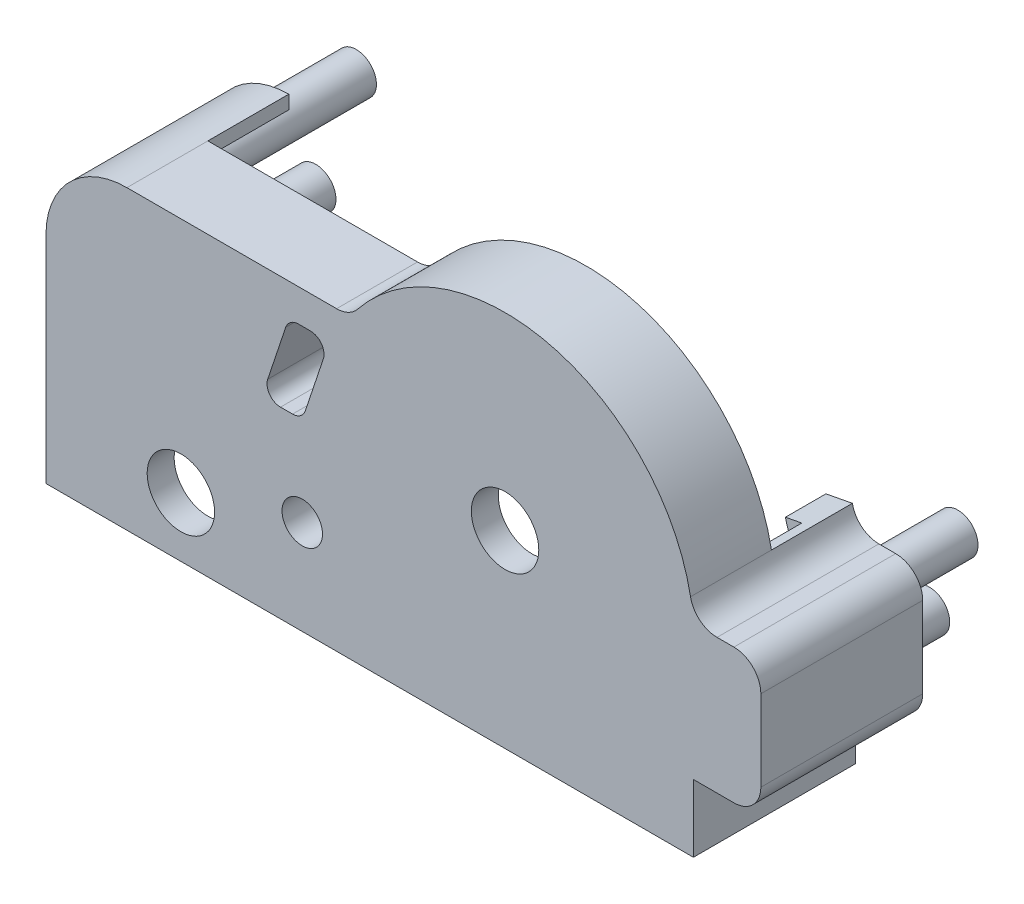
SolidWorks part; units mm, degrees
ref_plane "Front Plane" through (0, 0, 0) normal (0, 0, 1) x (1, 0, 0)
ref_plane "Top Plane" through (0, 0, 0) normal (0, 1, 0) x (1, 0, 0)
ref_plane "Right Plane" through (0, 0, 0) normal (1, 0, 0) x (0, 0, -1)
sketch "Sketch1" plane through (0, 0, 0) normal (0, 0, 1) x (1, 0, 0)
  line L0 (-17.0179, -7) -> (6.9821, -7)
  line L1 (-17.0179, -7) -> (-17.0179, 1)
  line L2 (-14.0179, 4) -> (-6.245, 4)
  line L3 (6.9821, -7) -> (6.9821, -4.5)
  line L4 (6.9821, -4.5) -> (8.4821, -4.5)
  line L5 (9.4821, -3.5) -> (9.4821, -0.5)
  line L6 (8.4821, 0.5) -> (7.8581, 0.5)
  arc A0 (-14.0179, 4) -> (-17.0179, 1) centre (-14.0179, 1) ccw
  arc A1 (6.8759, 1.3125) -> (-5.4644, 4.375) centre (0, 0) ccw
  arc A2 (9.4821, -0.5) -> (8.4821, 0.5) centre (8.4821, -0.5) ccw
  arc A3 (8.4821, -4.5) -> (9.4821, -3.5) centre (8.4821, -3.5) ccw
  arc A5 (-6.245, 4) -> (-5.4644, 4.375) centre (-6.245, 5) ccw
  arc A6 (6.8759, 1.3125) -> (7.8581, 0.5) centre (7.8581, 1.5) ccw
  point P8 (-17.0179, 4)
  point P15 (9.4821, 0.5)
  point P18 (9.4821, -4.5)
  point P21 (6.9821, -4.5)
  point P26 (6.9821, 0.5)
  dimension "D4" = 3
  dimension "D5" = 14
  dimension "D10" = 1
  dimension "D11" = 1
  dimension "D1" = 7
  dimension "D2" = 24
  dimension "D3" = 11
  dimension "D6" = 2.5
  dimension "D7" = 2.5
  dimension "D8" = 5
  dimension "D9" = 2.5
extrude "Boss-Extrude1" add sketch "Sketch1" along normal blind 6
shell "Shell1" thickness 1 removed face at (-5.0179, -7, 3) removed face at (0.4256, -0.539, 0)
sketch "Sketch2" plane through (0, 0, 5) normal (0, 0, -1) x (-1, 0, 0)
  line L0 (16.0179, -7) -> (-5.9821, -7) construction
  line L1 (17.0179, 1) -> (17.0179, -7) construction
  line L2 (7.2116, 2.8) -> (7.6575, 2.8)
  line L3 (6.7373, 2.1419) -> (7.4039, 0.1419)
  line L4 (8.1318, 2.4581) -> (8.7985, 0.4581)
  line L5 (7.8783, -0.2) -> (8.3242, -0.2)
  line L6 (6.245, 4) -> (14.0179, 4) construction
  circle A0 centre (0, 0) radius 1.25
  circle A1 centre (7.5179, -3.5) radius 0.75
  circle A2 centre (12.0179, -4.7966) radius 1.25
  arc A3 (6.7373, 2.1419) -> (7.2116, 2.8) centre (7.2116, 2.3) cw
  arc A4 (7.6575, 2.8) -> (8.1318, 2.4581) centre (7.6575, 2.3) cw
  arc A5 (8.7985, 0.4581) -> (8.3242, -0.2) centre (8.3242, 0.3) cw
  arc A6 (7.4039, 0.1419) -> (7.8783, -0.2) centre (7.8783, 0.3) ccw
  point P20 (6.5179, 2.8)
  point P23 (8.0179, 2.8)
  point P26 (9.0179, -0.2)
  dimension "D1" = 2.5
  dimension "D2" = 1.5
  dimension "D4" = 3.5
  dimension "D5" = 2.5
  dimension "D6" = 2.2034
  dimension "D7" = 5
  dimension "D13" = 0.5
  dimension "D3" = 9.5
  dimension "D8" = 9
  dimension "D9" = 8
  dimension "D10" = 3
  dimension "D11" = 1.5
  dimension "D12" = 1.2
extrude "Cut-Extrude1" cut sketch "Sketch2" against normal blind 6
sketch "Sketch3" plane through (0, -7, 0) normal (0, -1, 0) x (1, 0, 0)
  line L0 (-5.1962, 5) -> (-5.1962, 0) construction
  line L1 (5.9821, 5) -> (-5.1962, 5)
  line L2 (5.9821, 5) -> (5.9821, 2)
  line L3 (5.9821, 2) -> (-5.1962, 2)
  line L4 (-5.1962, 5) -> (-5.1962, 2)
  dimension "D1" = 3
extrude "Boss-Extrude2" add sketch "Sketch3" against normal blind 1
sketch "Sketch6" plane through (0, 0, 0) normal (0, 0, -1) x (-1, 0, 0)
  line L0 (6.245, 4) -> (14.0179, 4) construction
  line L1 (6.245, 3) -> (14.0179, 3) construction
  line L2 (6.245, 4) -> (14.0179, 4)
  line L3 (6.245, 3) -> (14.0179, 3)
  line L4 (-6.8759, 1.3125) -> (-5.8936, 1.125)
  line L5 (14.0179, 4) -> (14.0179, 3)
  arc A0 (5.4644, 4.375) -> (6.245, 4) centre (6.245, 5) ccw construction
  arc A1 (4.6837, 3.75) -> (6.245, 3) centre (6.245, 5) ccw construction
  arc A2 (4.6837, 3.75) -> (-5.8936, 1.125) centre (0, 0) ccw construction
  arc A3 (5.4644, 4.375) -> (-6.8759, 1.3125) centre (0, 0) ccw construction
  arc A4 (5.4644, 4.375) -> (6.245, 4) centre (6.245, 5) ccw
  arc A5 (4.6837, 3.75) -> (6.245, 3) centre (6.245, 5) ccw
  arc A6 (4.6837, 3.75) -> (-5.8936, 1.125) centre (0, 0) ccw
  arc A7 (5.4644, 4.375) -> (-6.8759, 1.3125) centre (0, 0) ccw
extrude "Cut-Extrude2" cut sketch "Sketch6" against normal blind 3
sketch "Sketch7" plane through (0, 0, 5) normal (0, 0, -1) x (-1, 0, 0)
  circle A0 centre (0, 0) radius 6
  circle A1 centre (0, 0) radius 7
  dimension "D1" = 12
  dimension "D2" = 14
extrude "Boss-Extrude4" add sketch "Sketch7" along normal blind 2
sketch "Sketch8" plane through (0, 0, 5) normal (0, 0, -1) x (-1, 0, 0)
  line L0 (7.6575, 2.8) -> (7.2116, 2.8) construction
  line L1 (8.7985, 0.4581) -> (8.1318, 2.4581) construction
  line L2 (7.8783, -0.2) -> (8.3242, -0.2) construction
  line L3 (6.7373, 2.1419) -> (7.4039, 0.1419) construction
  line L4 (7.6575, 2.8) -> (7.2116, 2.8)
  line L5 (8.7985, 0.4581) -> (8.1318, 2.4581)
  line L6 (7.8783, -0.2) -> (8.3242, -0.2)
  line L7 (6.7373, 2.1419) -> (7.4039, 0.1419)
  line L8 (5.9783, 1.8889) -> (6.645, -0.1111)
  line L9 (7.8783, -1) -> (8.3242, -1)
  line L10 (9.5575, 0.7111) -> (8.8908, 2.7111)
  line L11 (7.6575, 3.6) -> (7.2116, 3.6)
  circle A0 centre (7.5179, -3.5) radius 0.75 construction
  arc A1 (7.2116, 2.8) -> (6.7373, 2.1419) centre (7.2116, 2.3) ccw construction
  arc A2 (8.1318, 2.4581) -> (7.6575, 2.8) centre (7.6575, 2.3) ccw construction
  arc A3 (8.3242, -0.2) -> (8.7985, 0.4581) centre (8.3242, 0.3) ccw construction
  arc A4 (7.4039, 0.1419) -> (7.8783, -0.2) centre (7.8783, 0.3) ccw construction
  circle A5 centre (7.5179, -3.5) radius 0.75
  arc A6 (7.2116, 2.8) -> (6.7373, 2.1419) centre (7.2116, 2.3) ccw
  arc A7 (8.1318, 2.4581) -> (7.6575, 2.8) centre (7.6575, 2.3) ccw
  arc A8 (8.3242, -0.2) -> (8.7985, 0.4581) centre (8.3242, 0.3) ccw
  arc A9 (7.4039, 0.1419) -> (7.8783, -0.2) centre (7.8783, 0.3) ccw
  arc A10 (6.645, -0.1111) -> (7.8783, -1) centre (7.8783, 0.3) ccw
  arc A11 (8.3242, -1) -> (9.5575, 0.7111) centre (8.3242, 0.3) ccw
  arc A12 (8.8908, 2.7111) -> (7.6575, 3.6) centre (7.6575, 2.3) ccw
  arc A13 (7.2116, 3.6) -> (5.9783, 1.8889) centre (7.2116, 2.3) ccw
  circle A14 centre (7.5179, -3.5) radius 1.55
  dimension "D1" = 0.8
extrude "Boss-Extrude5" add sketch "Sketch8" along normal blind 2
sketch "Sketch10" plane through (0, 0, 5) normal (0, 0, -1) x (-1, 0, 0)
  line L0 (17.0179, 1) -> (17.0179, -7) construction
  line L1 (17.0179, -7) -> (16.0179, -7) construction
  line L2 (16.0179, 1) -> (16.0179, -7) construction
  line L3 (-9.4821, -3.5) -> (-9.4821, -0.5) construction
  line L5 (-8.4821, 0.5) -> (-7.8581, 0.5) construction
  line L6 (-5.9821, -7) -> (-6.9821, -7) construction
  circle A0 centre (-7.7821, -0.7) radius 0.75
  circle A1 centre (-6.7321, -3.7) radius 0.75
  circle A2 centre (16.0179, -1.5) radius 0.75
  circle A3 centre (14.5179, 2.9365) radius 0.75
  arc A4 (16.0179, 1) -> (14.0179, 3) centre (14.0179, 1) ccw construction
  dimension "D3" = 1.5
  dimension "D1" = 2.5
  dimension "D2" = 5.5
  dimension "D4" = 1.7
  dimension "D5" = 1.2
  dimension "D6" = 3.3
  dimension "D7" = 2.75
extrude "Boss-Extrude6" add sketch "Sketch10" along normal blind 8
sketch "Sketch11" plane through (0, 0, 5) normal (0, 0, -1) x (-1, 0, 0)
  line L0 (8.1318, 2.4581) -> (8.7985, 0.4581) construction
  line L1 (7.4039, 0.1419) -> (6.7373, 2.1419) construction
  line L2 (6.7373, 2.1419) -> (7.4039, 0.1419) construction
  circle A0 centre (7.8206, 1.1419) radius 0.7115
  point P8 (7.0706, 1.1419)
sketch "Sketch17" plane through (0, 0, 2) normal (0, 0, -1) x (-1, 0, 0)
  line L1 (-5.9821, -7) -> (5.1962, -7)
  line L2 (-5.9821, -7) -> (-5.9821, -6)
  line L3 (-5.9821, -6) -> (5.1962, -6)
  line L4 (5.1962, -7) -> (5.1962, -6)
extrude "Cut-Extrude5" cut sketch "Sketch17" against normal blind 1
sketch "Sketch18" plane through (0, 0, 5) normal (0, 0, -1) x (-1, 0, 0)
  line L0 (0, 0) -> (0, 8.6507) construction
  line L1 (2.2981, 4.0659) -> (3.7123, 5.4801)
  line L2 (-1.25, 4.5) -> (1.25, 4.5)
  line L3 (-1.25, 4.5) -> (-1.25, 6.5)
  line L4 (-1.25, 6.5) -> (1.25, 6.5)
  line L5 (1.25, 4.5) -> (1.25, 6.5)
  line L6 (2.2981, 4.0659) -> (4.0659, 2.2981)
  line L7 (4.0659, 2.2981) -> (5.4801, 3.7123)
  line L8 (3.7123, 5.4801) -> (5.4801, 3.7123)
  line L9 (4.5, 1.25) -> (6.5, 1.25)
  line L10 (4.5, 1.25) -> (4.5, -1.25)
  line L11 (4.5, -1.25) -> (6.5, -1.25)
  line L12 (6.5, 1.25) -> (6.5, -1.25)
  line L13 (4.0659, -2.2981) -> (5.4801, -3.7123)
  line L14 (4.0659, -2.2981) -> (2.2981, -4.0659)
  line L15 (2.2981, -4.0659) -> (3.7123, -5.4801)
  line L16 (5.4801, -3.7123) -> (3.7123, -5.4801)
  line L17 (1.25, -4.5) -> (1.25, -6.5)
  line L18 (1.25, -4.5) -> (-1.25, -4.5)
  line L19 (-1.25, -4.5) -> (-1.25, -6.5)
  line L20 (1.25, -6.5) -> (-1.25, -6.5)
  line L21 (-2.2981, -4.0659) -> (-3.7123, -5.4801)
  line L22 (-2.2981, -4.0659) -> (-4.0659, -2.2981)
  line L23 (-4.0659, -2.2981) -> (-5.4801, -3.7123)
  line L24 (-3.7123, -5.4801) -> (-5.4801, -3.7123)
  line L25 (-4.5, -1.25) -> (-6.5, -1.25)
  line L26 (-4.5, -1.25) -> (-4.5, 1.25)
  line L27 (-4.5, 1.25) -> (-6.5, 1.25)
  line L28 (-6.5, -1.25) -> (-6.5, 1.25)
  line L29 (-4.0659, 2.2981) -> (-5.4801, 3.7123)
  line L30 (-4.0659, 2.2981) -> (-2.2981, 4.0659)
  line L31 (-2.2981, 4.0659) -> (-3.7123, 5.4801)
  line L32 (-5.4801, 3.7123) -> (-3.7123, 5.4801)
  arc A0 (5.4644, 4.375) -> (-6.8759, 1.3125) centre (0, 0) ccw construction
  point P41 (0, 0)
  dimension "D1" = 6.5
  dimension "D2" = 1.25
  dimension "D3" = 2.5
  dimension "D4" = 2
  dimension "D5" = 3.7123
  dimension "D6" = 4.6704
extrude "Cut-Extrude7" cut sketch "Sketch18" along normal blind 3.5
